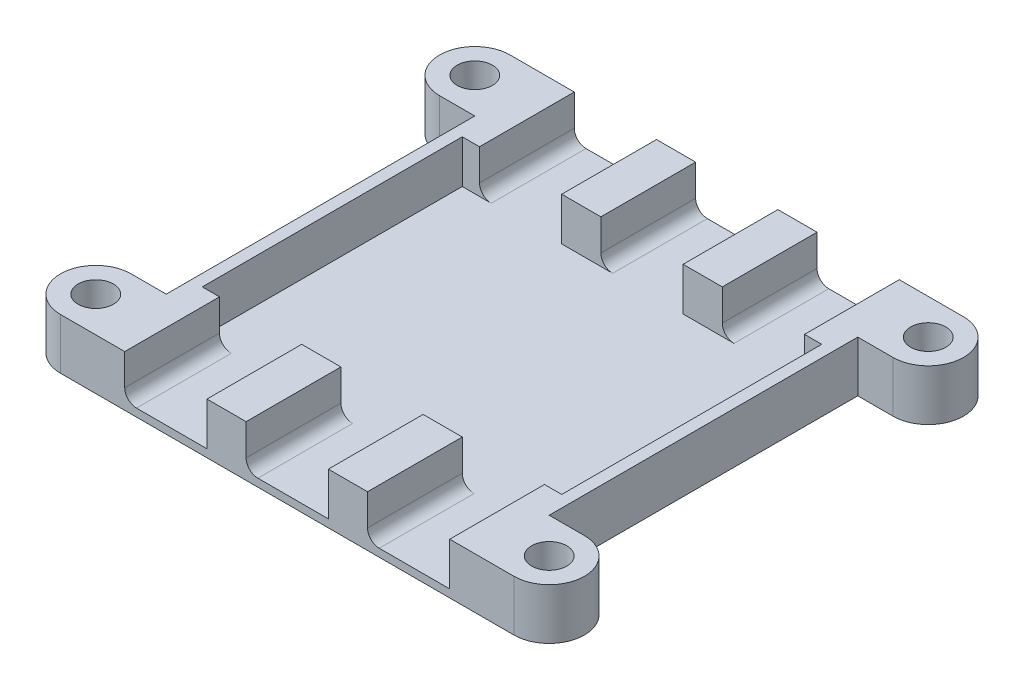
SolidWorks part; units mm, degrees
ref_plane "Front Plane" through (0, 0, 0) normal (0, 0, 1) x (1, 0, 0)
ref_plane "Top Plane" through (0, 0, 0) normal (0, 1, 0) x (1, 0, 0)
ref_plane "Right Plane" through (0, 0, 0) normal (1, 0, 0) x (0, 0, -1)
sketch "Sketch1" plane through (0, 0, 0) normal (0, 1, 0) x (1, 0, 0)
  line L0 (-22.95, 27.2) -> (-24.45, 27.2) construction
  line L1 (22.95, 16.6) -> (-22.95, 16.6)
  line L2 (22.95, 16.6) -> (22.95, -16.6)
  line L3 (22.95, -16.6) -> (-22.95, -16.6)
  line L4 (-22.95, 16.6) -> (-22.95, -16.6)
  line L5 (22.95, 16.6) -> (-22.95, -16.6) construction
  line L6 (22.95, -16.6) -> (-22.95, 16.6) construction
  line L7 (22.95, -27.2) -> (-22.95, -27.2)
  line L8 (22.95, -27.2) -> (22.95, 27.2)
  line L9 (22.95, 27.2) -> (-22.95, 27.2)
  line L10 (-22.95, -27.2) -> (-22.95, 27.2)
  line L11 (22.95, -27.2) -> (-22.95, 27.2) construction
  line L12 (22.95, 27.2) -> (-22.95, -27.2) construction
  line L13 (24.45, -28.7) -> (-24.45, -28.7)
  line L14 (24.45, -28.7) -> (24.45, 28.7)
  line L15 (24.45, 28.7) -> (-24.45, 28.7)
  line L16 (-24.45, -28.7) -> (-24.45, 28.7)
  line L17 (24.45, -28.7) -> (-24.45, 28.7) construction
  line L18 (24.45, 28.7) -> (-24.45, -28.7) construction
  line L19 (-22.95, 27.2) -> (-22.95, 28.7) construction
  point P0 (0, 0)
  point P6 (0, 0)
  point P11 (0, 0)
  dimension "D1" = 45.9
  dimension "D2" = 33.2
  dimension "D3" = 54.4
  dimension "D4" = 1.5
extrude "Boss-Extrude1" add sketch "Sketch1" along normal blind 1 contours L16 L13 L14 L15 L7 L10 L4 L9 L8 L2 | L10 L1 L8 L9 | L1 L4 L3 L2 | L10 L7 L8 L3 region at (0, 0, 0) region at (0, 0, -21.9) region at (0, 0, 21.9) region at (0, 0, 27.9459)
sketch "Sketch2" plane through (0, 1, 0) normal (0, 1, 0) x (1, 0, 0)
  line L0 (-24.45, -28.7) -> (-24.45, 28.7) construction
  line L1 (24.45, -16.6) -> (-24.45, -16.6)
  line L2 (24.45, -16.6) -> (24.45, 16.6)
  line L3 (24.45, 16.6) -> (-24.45, 16.6)
  line L4 (-24.45, -16.6) -> (-24.45, 16.6)
  line L5 (24.45, -16.6) -> (-24.45, 16.6) construction
  line L6 (24.45, 16.6) -> (-24.45, -16.6) construction
  line L7 (-22.95, 27.2) -> (-24.45, 27.2) construction
  line L8 (22.95, -27.2) -> (-22.95, -27.2)
  line L9 (22.95, -27.2) -> (22.95, 27.2)
  line L10 (22.95, 27.2) -> (-22.95, 27.2)
  line L11 (-22.95, -27.2) -> (-22.95, 27.2)
  line L12 (22.95, -27.2) -> (-22.95, 27.2) construction
  line L13 (22.95, 27.2) -> (-22.95, -27.2) construction
  line L14 (-22.95, 27.2) -> (-22.95, 28.7) construction
  line L15 (24.45, 28.7) -> (-24.45, 28.7) construction
  line L16 (0, 28.7) -> (0, -28.7) construction
  line L17 (24.45, -28.7) -> (-24.45, -28.7) construction
  line L18 (-15.5, 28.7) -> (-15.5, -28.7) construction
  line L19 (-5.25, 16.6) -> (5.25, 16.6)
  line L20 (-5.25, 16.6) -> (-5.25, 28.7)
  line L21 (-5.25, 28.7) -> (5.25, 28.7)
  line L22 (5.25, 16.6) -> (5.25, 28.7)
  line L23 (-5.25, 16.6) -> (5.25, 28.7) construction
  line L24 (-5.25, 28.7) -> (5.25, 16.6) construction
  line L25 (-24.45, 22.65) -> (24.45, 22.65) construction
  line L26 (24.45, -28.7) -> (24.45, 28.7) construction
  line L27 (20.75, 28.7) -> (10.25, 28.7)
  line L28 (-20.75, 16.6) -> (-10.25, 16.6)
  line L29 (-20.75, 16.6) -> (-20.75, 28.7)
  line L30 (-20.75, 28.7) -> (-10.25, 28.7)
  line L31 (-10.25, 16.6) -> (-10.25, 28.7)
  line L32 (-20.75, 16.6) -> (-10.25, 28.7) construction
  line L33 (-20.75, 28.7) -> (-10.25, 16.6) construction
  line L34 (20.75, 16.6) -> (20.75, 28.7)
  line L35 (10.25, 16.6) -> (10.25, 28.7)
  line L36 (-24.45, 0) -> (24.45, 0) construction
  line L37 (20.75, -16.6) -> (20.75, -28.7)
  line L38 (10.25, -16.6) -> (10.25, -28.7)
  line L39 (5.25, -16.6) -> (5.25, -28.7)
  line L40 (-5.25, -16.6) -> (-5.25, -28.7)
  line L41 (-10.25, -16.6) -> (-10.25, -28.7)
  line L42 (-20.75, -16.6) -> (-20.75, -28.7)
  point P0 (0, 0)
  point P8 (0, 0)
  point P21 (0, 22.65)
  point P32 (-15.5, 22.65)
  line M17 (-24.45, 28.7) -> (-24.45, -28.7)
  line M18 (-24.45, -28.7) -> (24.45, -28.7)
  line M19 (24.45, -28.7) -> (24.45, 28.7)
  line M20 (24.45, 28.7) -> (-24.45, 28.7)
  dimension "D1" = 33.2
  dimension "D2" = 1.5
  dimension "D3" = 10.5
  dimension "D4" = 5
extrude "Boss-Extrude2" add sketch "Sketch2" along normal blind 5.5 contours L10 L29 L3 L11 M20 M17 | L1 L11 L3 M17 | L42 L8 L11 L1 M17 M18 | L8 L41 L40 M18 | L8 L39 L38 M18 | L8 L37 L1 L9 M18 M19 | L9 L1 L3 M19 | L34 L10 L9 L3 M19 M20 | L10 L35 L22 M20 | L31 L10 L20 M20 | L31 L3 L20 L10 | L3 L35 L10 L22 | L1 L39 L8 L38 | L1 L41 L8 L40 | L3 L29 L10 L11 | L34 L3 L9 L10 | L1 L37 L8 L9 | L42 L1 L11 L8 region at (21.85, 1, 21.9) region at (7.75, 1, 21.9) region at (23.7, 1, 0) region at (23.4154, 1, 23.4654) region at (7.75, 1, 27.95) region at (23.4154, 1, -23.4654) region at (21.85, 1, -21.9) region at (-7.75, 1, 21.9) region at (-7.75, 1, 27.95) region at (7.75, 1, -21.9) region at (-21.85, 1, 21.9) region at (7.75, 1, -27.95) region at (-23.4154, 1, 23.4654) region at (-23.7, 1, 0) region at (-7.75, 1, -21.9) region at (-21.85, 1, -21.9) region at (-23.4154, 1, -23.4654) region at (-7.75, 1, -27.95)
sketch "Sketch4" plane through (0, 0, 0) normal (0, -1, 0) x (1, 0, 0)
  line L0 (-28.95, 28.7) -> (-24.45, 28.7)
  line L1 (-24.45, 28.7) -> (-24.45, -28.7) construction
  line L3 (-28.95, 19.7) -> (-24.45, 19.7)
  line L5 (0, 28.7) -> (0, -28.7) construction
  line L6 (24.45, 28.7) -> (-24.45, 28.7) construction
  line L7 (24.45, -28.7) -> (-24.45, -28.7) construction
  line L8 (-24.45, 0) -> (24.45, 0) construction
  line L9 (24.45, 28.7) -> (24.45, -28.7) construction
  line L10 (28.95, 28.7) -> (24.45, 28.7)
  line L11 (28.95, 19.7) -> (24.45, 19.7)
  line L12 (-28.95, -19.7) -> (-24.45, -19.7)
  line L13 (-28.95, -28.7) -> (-24.45, -28.7)
  line L14 (28.95, -28.7) -> (24.45, -28.7)
  line L15 (28.95, -19.7) -> (24.45, -19.7)
  circle A0 centre (-28.95, 24.2) radius 4.5
  circle A1 centre (-28.95, 24.2) radius 2.25
  circle A2 centre (28.95, 24.2) radius 2.25
  circle A3 centre (28.95, 24.2) radius 4.5
  circle A4 centre (-28.95, -24.2) radius 2.25
  circle A5 centre (-28.95, -24.2) radius 4.5
  circle A6 centre (28.95, -24.2) radius 2.25
  circle A7 centre (28.95, -24.2) radius 4.5
  line M8 (-24.45, 28.7) -> (-24.45, -28.7)
  line M10 (24.45, -28.7) -> (24.45, 28.7)
  dimension "D1" = 9
  dimension "D2" = 4.5
extrude "Boss-Extrude3" add sketch "Sketch4" against normal up to surface (6.5 mm away) contours A0 L0 M8 | A0 L3 M8 | A0 A1 | A3 L10 M10 | A3 A2 | L11 A3 M10 | A7 A6 | A7 L14 M10 | A7 L15 M10 | A5 L13 M8 | L12 A5 M8 | A5 A4 region at (-25.4552, 0, -20.7052) region at (-25.4552, 0, 27.6948) region at (-25.858, 0, 27.292) region at (-25.4552, 0, 20.7052) region at (-25.858, 0, -21.108) region at (-25.4552, 0, -27.6948) region at (25.4552, 0, 27.6948) region at (25.4552, 0, -20.7052) region at (32.042, 0, 27.292) region at (25.4552, 0, 20.7052) region at (32.042, 0, -21.108) region at (25.4552, 0, -27.6948) up to face at (-22.225, 6.5, 0)
fillet "Fillet1" radius 1.5 6 edges at (-20.75, 1, 22.65) (-5.25, 1, 22.65) (10.25, 1, 22.65) (10.25, 1, -22.65) (-5.25, 1, -22.65) (-20.75, 1, -22.65)
